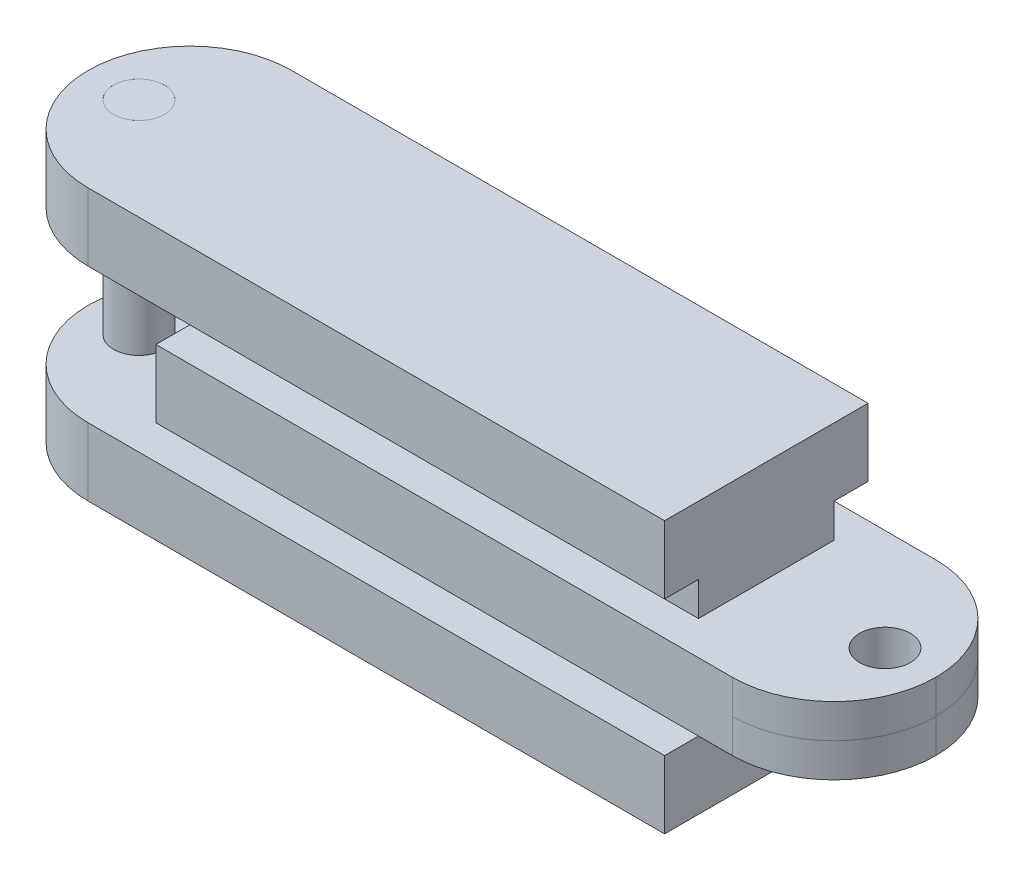
SolidWorks part; units mm, degrees
ref_plane "Front Plane" through (0, 0, 0) normal (0, 0, 1) x (1, 0, 0)
ref_plane "Top Plane" through (0, 0, 0) normal (0, 1, 0) x (1, 0, 0)
ref_plane "Right Plane" through (0, 0, 0) normal (1, 0, 0) x (0, 0, -1)
sketch "Sketch1" plane through (0, 0, 0) normal (0, 0, 1) x (1, 0, 0)
  line L0 (-100, 0) -> (150, 0) construction
  line L10 (-100, 0) -> (-100, 20)
  line L11 (-100, 20) -> (-50, 20)
  line L12 (-50, 20) -> (-50, 40)
  line L13 (-50, 40) -> (150, 40)
  line L14 (150, 40) -> (150, 30)
  line L15 (150, 30) -> (100, 30)
  line L16 (100, 30) -> (100, 0)
  line L17 (100, 0) -> (-100, 0)
  point P8 (0, 0)
  dimension "D1" = 50
  dimension "D2" = 50
  dimension "D3" = 200
  dimension "D4" = 20
  dimension "D5" = 40
  dimension "D6" = 10
extrude "Boss-Extrude1" add sketch "Sketch1" along normal blind 30 and the other way blind 30
sketch "Sketch2" plane through (0, 40, 0) normal (0, 1, 0) x (1, 0, 0)
  line L0 (150, 30) -> (-50, 30) construction
  line L1 (150, 30) -> (150, -30) construction
  circle A0 centre (135, 0) radius 7.5
  dimension "D1" = 30
  dimension "D2" = 15
extrude "Cut-Extrude1" cut sketch "Sketch2" against normal through all both and the other way through all
fillet "Fillet6" radius 30 1 edges at (150, 35, 30)
fillet "Fillet7" radius 30 1 edges at (150, 35, -30)
sketch "Sketch3" plane through (0, 20, 0) normal (0, 1, 0) x (1, 0, 0)
  line L0 (-100, 30) -> (-100, -30) construction
  line L1 (-50, 30) -> (-100, 30) construction
  circle A0 centre (-85, 0) radius 7.5
  dimension "D1" = 15
  dimension "D2" = 30
extrude "Cut-Extrude2" cut sketch "Sketch3" against normal through all both and the other way through all
fillet "Fillet8" radius 30 1 edges at (-100, 10, -30)
fillet "Fillet9" radius 30 1 edges at (-100, 10, 30)
mirror "Mirror1" about plane through (-50, 40, -30) normal (0, 1, 0) of "Cut-Extrude1", "Cut-Extrude2", "Fillet8", "Fillet7", "Boss-Extrude1", "Fillet9", "Fillet6"
sketch "Sketch16" plane through (0, 0, -30) normal (0, 0, -1) x (-1, 0, 0)
  line L1 (50, 20) -> (-100, 20)
  line L2 (50, 20) -> (50, 30)
  line L3 (50, 30) -> (-100, 30)
  line L4 (-100, 20) -> (-100, 30)
extrude "Cut-Extrude11" cut sketch "Sketch16" against normal blind 10
sketch "Sketch17" plane through (0, 0, -30) normal (0, 0, -1) x (-1, 0, 0)
  line L1 (50, 60) -> (-100, 60)
  line L2 (50, 60) -> (50, 50)
  line L3 (50, 50) -> (-100, 50)
  line L4 (-100, 60) -> (-100, 50)
extrude "Cut-Extrude12" cut sketch "Sketch17" against normal blind 10
sketch "Sketch18" plane through (0, 0, 30) normal (0, 0, 1) x (1, 0, 0)
  line L1 (-50, 60) -> (100, 60)
  line L2 (-50, 60) -> (-50, 50)
  line L3 (-50, 50) -> (100, 50)
  line L4 (100, 60) -> (100, 50)
extrude "Cut-Extrude13" cut sketch "Sketch18" against normal blind 10
sketch "Sketch19" plane through (0, 0, 30) normal (0, 0, 1) x (1, 0, 0)
  line L1 (-50, 20) -> (100, 20)
  line L2 (-50, 20) -> (-50, 30)
  line L3 (-50, 30) -> (100, 30)
  line L4 (100, 20) -> (100, 30)
extrude "Cut-Extrude14" cut sketch "Sketch19" against normal blind 10
sketch "Sketch21" plane through (0, 20, 0) normal (0, 1, 0) x (1, 0, 0)
  circle A0 centre (-85, 0) radius 7.5
extrude "Boss-Extrude2" add sketch "Sketch21" along normal blind 60 and the other way blind 20 separate body
